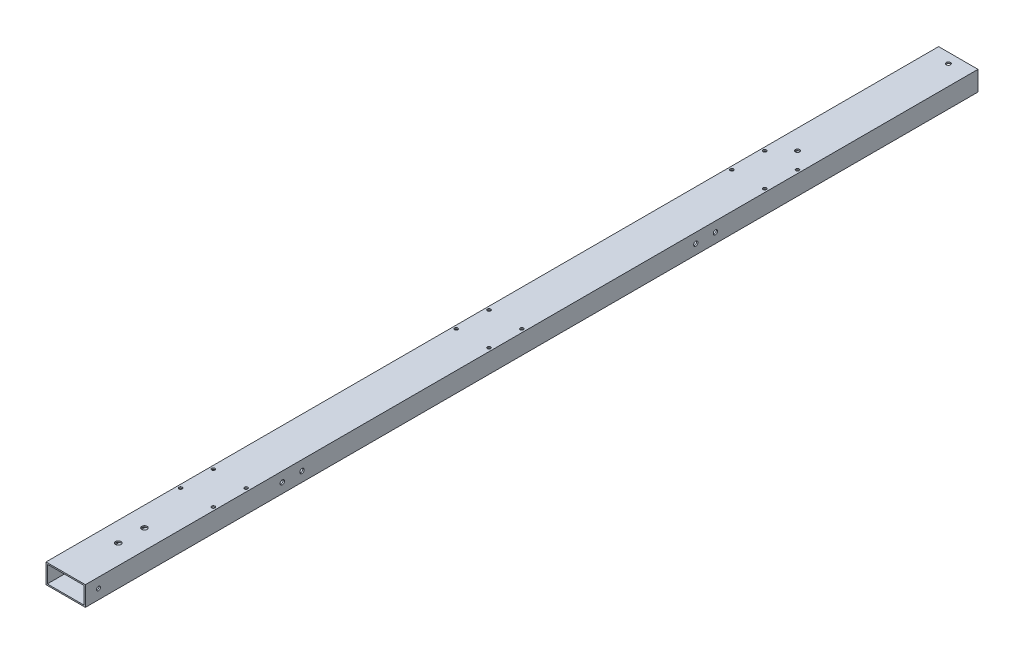
SolidWorks part; units mm, degrees
material "1060 合金"
ref_plane "前视基准面" through (0, 0, 0) normal (0, 0, 1) x (1, 0, 0)
ref_plane "上视基准面" through (0, 0, 0) normal (0, 1, 0) x (1, 0, 0)
ref_plane "右视基准面" through (0, 0, 0) normal (1, 0, 0) x (0, 0, -1)
other "Configuration Table"
sketch "草图1" plane through (0, 0, 0) normal (0, 0, 1) x (1, 0, 0)
  line L1 (0, 0) -> (30, 0)
  line L2 (0, 0) -> (0, -15)
  line L3 (0, -15) -> (30, -15)
  line L4 (30, 0) -> (30, -15)
  dimension "D1" = 15
  dimension "D2" = 30
extrude "拉伸-薄壁1" add sketch "草图1" along normal blind 800 thin thin type one direction reverse wall 1
sketch "草图2" plane through (0, -15, 0) normal (0, -1, 0) x (1, 0, 0)
  circle A1 centre (7.5, 825) radius 2.6
  circle A2 centre (7.5, 825) radius 2.6
  dimension "D1" = 0
extrude "切除-拉伸1" [suppressed] cut sketch "草图2" against normal up to next
sketch "草图3" plane through (0, 0, 0) normal (-1, 0, 0) x (0, 0, 1)
  line L0 (800, 0) -> (0, 0) construction
  line L1 (0, 0) -> (0, -15) construction
  circle A0 centre (215, -7.5) radius 1.7
  circle A1 centre (170, -7.5) radius 1.7
  dimension "D1" = 3.4
  dimension "D2" = 3.4
  dimension "D3" = 45
  dimension "D4" = 7.5
  dimension "D5" = 7.5
  dimension "D6" = 170
sketch "草图4" plane through (30, 0, 0) normal (1, 0, 0) x (0, 0, -1)
  line L0 (-800, -15) -> (0, -15) construction
  line L1 (-800, -15) -> (-800, 0) construction
  circle A0 centre (-790, -7.5) radius 1.5
  dimension "D1" = 3
  dimension "D2" = 7.5
  dimension "D3" = 10
extrude "切除-拉伸3" cut sketch "草图4" against normal through all
sketch "草图5" plane through (30, 0, 0) normal (1, 0, 0) x (0, 0, -1)
  line L0 (-800, 0) -> (0, 0) construction
  line L1 (0, -15) -> (0, 0) construction
  line L2 (-800, -1) -> (-800, -14) construction
  circle A0 centre (-320, -7.5) radius 1.65
  circle A1 centre (-335, -7.5) radius 1.65
  circle A2 centre (-635, -7.5) radius 1.65
  circle A3 centre (-650, -7.5) radius 1.65
  dimension "D1" = 3.3
  dimension "D4" = 3.3
  dimension "D7" = 7.5
  dimension "D9" = 3.3
  dimension "D10" = 3.3
  dimension "D2" = 7.5
  dimension "D3" = 15
  dimension "D5" = 7.5
  dimension "D6" = 320
  dimension "D8" = 7.5
  dimension "D11" = 15
  dimension "D12" = 150
extrude "切除-拉伸4" cut sketch "草图5" against normal through all
sketch "草图6" plane through (0, 0, 0) normal (0, 0, -1) x (-1, 0, 0)
  line L4 (0, -15) -> (0, 0)
  line L5 (0, 0) -> (-30, 0)
  line L6 (-30, 0) -> (-30, -15)
  line L7 (-30, -15) -> (0, -15)
  line L8 (0, -15) -> (0, 0)
  line L9 (0, 0) -> (-30, 0)
  line L10 (-30, 0) -> (-30, -15)
  line L11 (-30, -15) -> (0, -15)
  dimension "D1" = 0
extrude "切除-拉伸5" cut sketch "草图6" against normal blind 300
sketch "草图7" [suppressed] plane through (0, 0, 0) normal (0, 1, 0) x (1, 0, 0)
  line L0 (15, -300) -> (15, -861.2957) construction
  line L1 (0, -300) -> (30, -300) construction
  line L2 (0, -550) -> (263.5539, -550) construction
  line L3 (0, -800) -> (0, -300) construction
  circle A0 centre (7.5, -545) radius 1.25
  circle A1 centre (22.5, -545) radius 1.25
  circle A2 centre (22.5, -555) radius 1.25
  circle A3 centre (7.5, -555) radius 1.25
  circle A4 centre (7.5, -405) radius 1.25
  circle A5 centre (22.5, -405) radius 1.25
  circle A6 centre (22.5, -415) radius 1.25
  circle A7 centre (7.5, -415) radius 1.25
  circle A8 centre (7.5, -685) radius 1.25
  circle A9 centre (22.5, -685) radius 1.25
  circle A10 centre (22.5, -695) radius 1.25
  circle A11 centre (7.5, -695) radius 1.25
  circle A12 centre (7.5, -545) radius 1.25
  circle A13 centre (22.5, -545) radius 1.25
  circle A14 centre (22.5, -555) radius 1.25
  circle A15 centre (7.5, -555) radius 1.25
  line M12 (0, -300) -> (0, -800)
  line M14 (30, -800) -> (30, -300)
  dimension "D1" = 2.5
  dimension "D3" = 15
  dimension "D4" = 10
  dimension "D2" = 250
  dimension "D6" = 135
  dimension "D5" = 2
extrude "切除-拉伸6" [suppressed] cut sketch "草图7" against normal blind 155 contours A4 M12 | A7 M12 | A5 M14 | A6 M14 | A1 M14 | A0 M12 | A2 M14 | A8 M12 | A11 M12 | A9 M14 | A10 M14 | A3
sketch "草图8" plane through (0, 0, 300) normal (0, 0, -1) x (-1, 0, 0)
  line L0 (-1, -14) -> (-1, -1) construction
  line L1 (-1, -1) -> (-29, -1) construction
  line L2 (-29, -1) -> (-29, -14) construction
  line L3 (-29, -14) -> (-1, -14) construction
  line L4 (-30, -15) -> (0, -15)
  line L5 (0, -15) -> (0, 0)
  line L6 (0, 0) -> (-30, 0)
  line L7 (-30, 0) -> (-30, -15)
  line L8 (-30, -15) -> (0, -15)
  line L9 (0, -15) -> (0, 0)
  line L10 (0, 0) -> (-30, 0)
  line L11 (-30, 0) -> (-30, -15)
  line L12 (-1, -14) -> (-1, -1)
  line L13 (-1, -1) -> (-29, -1)
  line L14 (-29, -1) -> (-29, -14)
  line L15 (-29, -14) -> (-1, -14)
  dimension "D1" = 0
extrude "凸台-拉伸1" add sketch "草图8" along normal blind 180
sketch "草图9" plane through (0, 0, 0) normal (0, 1, 0) x (1, 0, 0)
  line L0 (0, -800) -> (0, -120) construction
  line L1 (30, -800) -> (0, -800) construction
  circle A0 centre (15, -740) radius 2.05
  circle A1 centre (15, -760) radius 2.05
  dimension "D1" = 4.1
  dimension "D2" = 15
  dimension "D3" = 60
  dimension "D4" = 2
extrude "切除-拉伸7" cut sketch "草图9" against normal blind 10
sketch "草图10" plane through (0, -15, 0) normal (0, -1, 0) x (1, 0, 0)
  line L0 (15, 735) -> (15, 760) construction
  line L1 (8, 735) -> (8, 760)
  line L2 (22, 735) -> (22, 760)
  line L3 (0, 800) -> (0, 120) construction
  line L4 (0, 800) -> (30, 800) construction
  arc A0 (8, 735) -> (22, 735) centre (15, 735) ccw
  arc A1 (22, 760) -> (8, 760) centre (15, 760) ccw
  point P2 (15, 747.5)
  dimension "D3" = 7
  dimension "D1" = 25
  dimension "D2" = 15
  dimension "D4" = 40
extrude "切除-拉伸8" cut sketch "草图10" against normal blind 10
sketch "草图11" plane through (0, -15, 0) normal (0, -1, 0) x (1, 0, 0)
  line L0 (0, 800) -> (0, 120) construction
  line L1 (30, 120) -> (0, 120) construction
  circle A0 centre (15, 127.5) radius 1.6
  circle A1 centre (15, 242.5) radius 1.6
  dimension "D1" = 3.2
  dimension "D2" = 15
  dimension "D3" = 7.5
  dimension "D4" = 2
extrude "切除-拉伸9" cut sketch "草图11" against normal through all
sketch "草图12" plane through (0, -15, 0) normal (0, -1, 0) x (1, 0, 0)
  line L0 (15, 247) -> (15, 237) construction
  line L1 (22, 247) -> (22, 237)
  line L2 (8, 247) -> (8, 237)
  line L3 (30, 120) -> (0, 120) construction
  line L4 (30, 800) -> (30, 120) construction
  arc A0 (22, 247) -> (8, 247) centre (15, 247) ccw
  arc A1 (8, 237) -> (22, 237) centre (15, 237) ccw
  point P2 (15, 242)
  dimension "D1" = 7
  dimension "D2" = 117
  dimension "D3" = 10
  dimension "D4" = 15
extrude "切除-拉伸10" cut sketch "草图12" against normal up to next
sketch "草图13" plane through (0, -15, 0) normal (0, -1, 0) x (1, 0, 0)
  line L0 (30, 800) -> (30, 120) construction
  line L1 (0, 800) -> (30, 800) construction
  circle A0 centre (27.5, 700) radius 1.25
  circle A1 centre (2.5, 700) radius 1.25
  circle A2 centre (2.5, 675) radius 1.25
  circle A3 centre (27.5, 675) radius 1.25
  circle A4 centre (27.5, 465) radius 1.25
  circle A5 centre (27.5, 490) radius 1.25
  circle A6 centre (2.5, 490) radius 1.25
  circle A7 centre (2.5, 465) radius 1.25
  circle A8 centre (27.5, 255) radius 1.25
  circle A9 centre (27.5, 280) radius 1.25
  circle A10 centre (2.5, 280) radius 1.25
  circle A11 centre (2.5, 255) radius 1.25
  dimension "D1" = 2.5
  dimension "D2" = 2.5
  dimension "D3" = 100
  dimension "D4" = 2
  dimension "D5" = 2
  dimension "D6" = 3
extrude "切除-拉伸11" cut sketch "草图13" against normal through all
